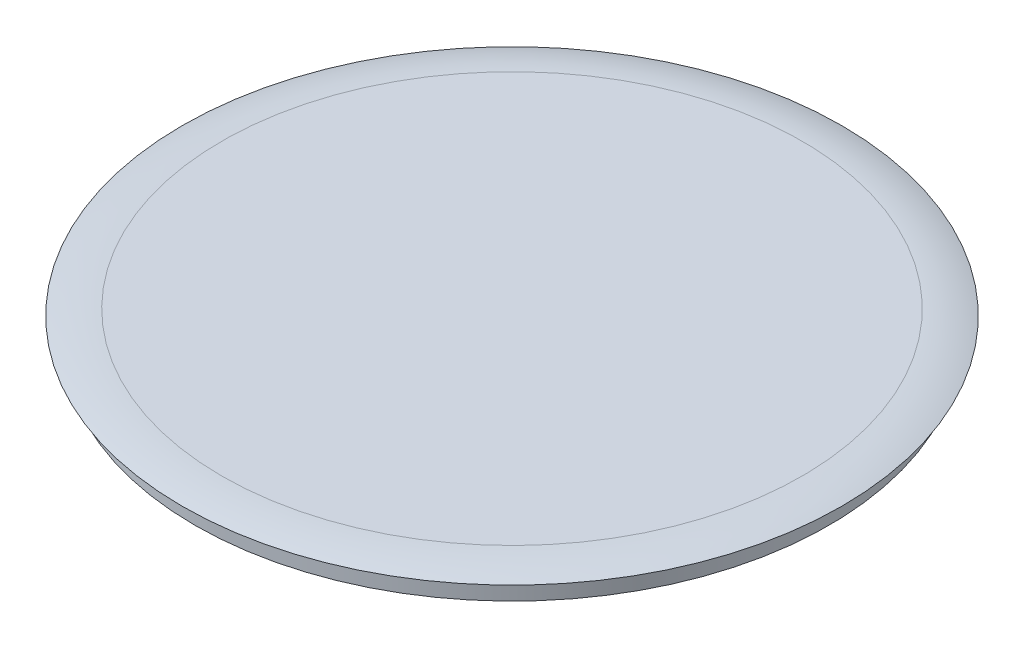
SolidWorks part; units mm, degrees
ref_plane "Front Plane" through (0, 0, 0) normal (0, 0, 1) x (1, 0, 0)
ref_plane "Top Plane" through (0, 0, 0) normal (0, 1, 0) x (1, 0, 0)
ref_plane "Right Plane" through (0, 0, 0) normal (1, 0, 0) x (0, 0, -1)
sketch "Sketch1" plane through (0, 0, 0) normal (0, 1, 0) x (1, 0, 0)
  circle A0 centre (0, 0) radius 25
  dimension "D1" = 50
extrude "Boss-Extrude1" add sketch "Sketch1" along normal blind 1.8
sketch "Sketch2" plane through (0, 1.8, 0) normal (0, 1, 0) x (1, 0, 0)
  circle A0 centre (0, 0) radius 26
  dimension "D1" = 52
extrude "Boss-Extrude2" add sketch "Sketch2" along normal blind 0.5
fillet "Fillet1" radius 10 1 edges at (0, 2.3, 26)
